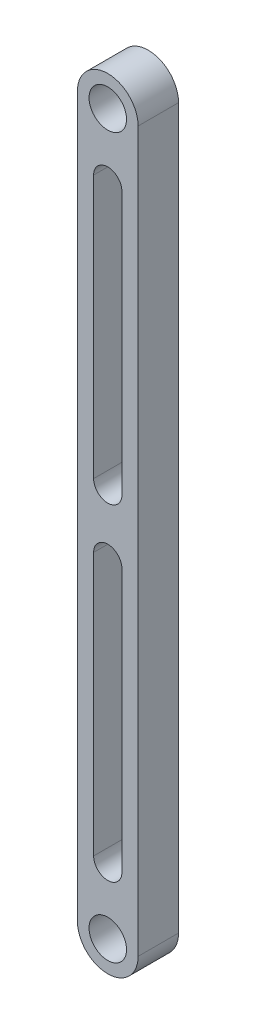
SolidWorks part; units mm, degrees
material "PEI"
ref_plane "Front Plane" through (0, 0, 0) normal (0, 0, 1) x (1, 0, 0)
ref_plane "Top Plane" through (0, 0, 0) normal (0, 1, 0) x (1, 0, 0)
ref_plane "Right Plane" through (0, 0, 0) normal (1, 0, 0) x (0, 0, -1)
sketch "Sketch1" plane through (0, 0, 0) normal (0, 0, 1) x (1, 0, 0)
  line L0 (0, -88.9) -> (0, 88.9) construction
  line L1 (-7.5, -88.9) -> (-7.5, 88.9)
  line L2 (7.5, -88.9) -> (7.5, 88.9)
  line L3 (0, -72.9) -> (0, -7.9) construction
  line L4 (-3.5, -72.9) -> (-3.5, -7.9)
  line L5 (3.5, -72.9) -> (3.5, -7.9)
  line L6 (0, 72.9) -> (0, 7.9) construction
  line L7 (3.5, 72.9) -> (3.5, 7.9)
  line L8 (-3.5, 72.9) -> (-3.5, 7.9)
  line L9 (-3.5, 40.4) -> (3.5, 40.4) construction
  line L10 (-3.5, -40.4) -> (3.5, -40.4) construction
  line L11 (-4.635, -88.9) -> (-3.5, -72.9) construction
  line L12 (-4.635, 88.9) -> (-3.5, 72.9) construction
  arc A0 (-7.5, -88.9) -> (7.5, -88.9) centre (0, -88.9) ccw
  arc A1 (7.5, 88.9) -> (-7.5, 88.9) centre (0, 88.9) ccw
  circle A2 centre (0, -88.9) radius 4.635
  circle A3 centre (0, 88.9) radius 4.635
  arc A4 (-3.5, -72.9) -> (3.5, -72.9) centre (0, -72.9) ccw
  arc A5 (3.5, -7.9) -> (-3.5, -7.9) centre (0, -7.9) ccw
  arc A6 (3.5, 72.9) -> (-3.5, 72.9) centre (0, 72.9) ccw
  arc A7 (-3.5, 7.9) -> (3.5, 7.9) centre (0, 7.9) ccw
  point P2 (0, 0)
  point P14 (0, -40.4)
  point P19 (0, 40.4)
  dimension "D3" = 9.27
  dimension "D1" = 177.8
  dimension "D2" = 15
  dimension "D4" = 7
  dimension "60" = 65
  dimension "D6" = 16
extrude "Boss-Extrude1" add sketch "Sketch1" along normal blind 10
